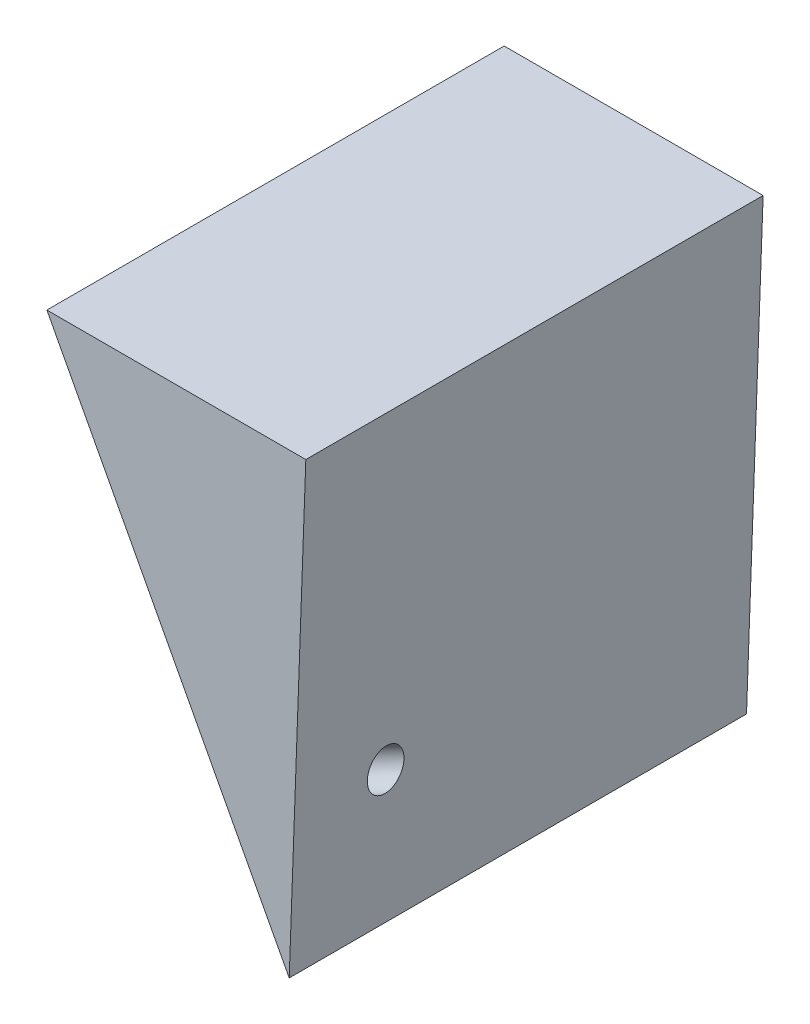
SolidWorks part; units mm, degrees
ref_plane "Front Plane" through (0, 0, 0) normal (0, 0, 1) x (1, 0, 0)
ref_plane "Top Plane" through (0, 0, 0) normal (0, 1, 0) x (1, 0, 0)
ref_plane "Right Plane" through (0, 0, 0) normal (1, 0, 0) x (0, 0, -1)
sketch "Sketch1" plane through (0, 0, 0) normal (0, 0, 1) x (1, 0, 0)
  line L0 (-36.2386, 19.2413) -> (-9.7428, -30.7587)
  line L1 (-9.7428, -30.7587) -> (-7.9267, 19.2413)
  line L2 (-7.9267, 19.2413) -> (-36.2386, 19.2413)
  dimension "D1" = 50
  dimension "D2" = 50
  dimension "D3" = 30
extrude "Boss-Extrude1" add sketch "Sketch1" along normal blind 50
sketch "Sketch2" plane through (-20.3326, -10.7746, 0) normal (-0.8836, -0.4682, 0) x (0, 0, 1)
  line L0 (50, 33.97) -> (50, -22.6165) construction
  line L1 (50, -22.6165) -> (0, -22.6165) construction
  circle A0 centre (40, -9.6165) radius 2
  dimension "D1" = 4
  dimension "D2" = 10
  dimension "D3" = 13
extrude "Cut-Extrude1" cut sketch "Sketch2" against normal blind 50
